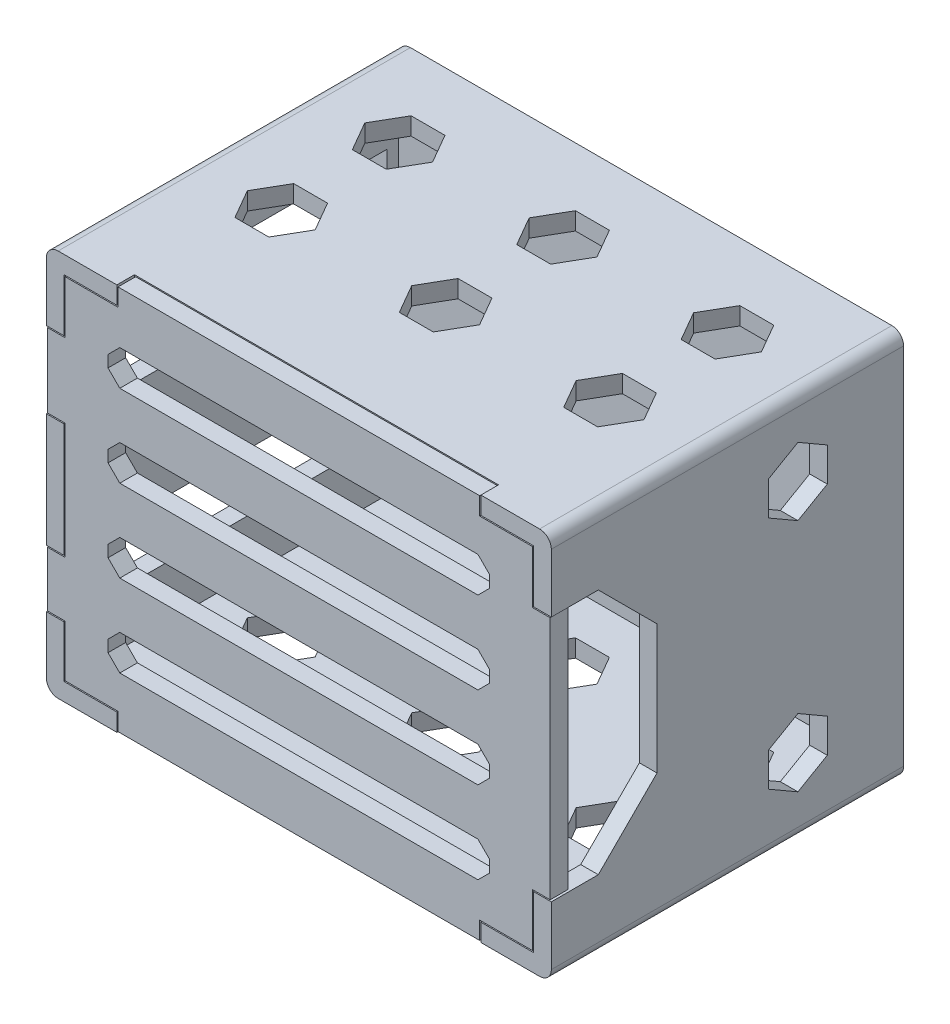
SolidWorks part; units mm, degrees
ref_plane "Front Plane" through (0, 0, 0) normal (0, 0, 1) x (1, 0, 0)
ref_plane "Top Plane" through (0, 0, 0) normal (0, 1, 0) x (1, 0, 0)
ref_plane "Right Plane" through (0, 0, 0) normal (1, 0, 0) x (0, 0, -1)
sketch "Sketch1" plane through (0, 0, 0) normal (0, 0, 1) x (1, 0, 0)
  line L0 (-43, -33) -> (-43, 33)
  line L1 (-40, -30) -> (40, -30)
  line L2 (-40, -30) -> (-40, 30)
  line L3 (-40, 30) -> (40, 30)
  line L4 (40, -30) -> (40, 30)
  line L5 (-40, -30) -> (40, 30) construction
  line L6 (-40, 30) -> (40, -30) construction
  line L7 (-43, 33) -> (43, 33)
  line L8 (43, -33) -> (43, 33)
  line L9 (-43, -33) -> (43, -33)
  point P0 (0, 0)
  dimension "D1" = 60
  dimension "125" = 80
  dimension "D3" = 3
extrude "Boss-Extrude1" add sketch "Sketch1" along normal blind 60
extrude "Boss-Extrude2" add sketch "Sketch1<2>" along normal blind 3 contours L1 L4 L3 L2 region at (0, 0, 0)
sketch "Sketch1<2>" plane through (0, 0, 0) normal (0, 0, 1) x (1, 0, 0) same geometry as "Sketch1"
sketch "Sketch2" plane through (-43, 0, 0) normal (-1, 0, 0) x (0, 0, 1)
  line L0 (60, 33) -> (60, -33) construction
  line L1 (60, -11.4) -> (5, -11.4)
  line L2 (60, -11.4) -> (60, -21.2)
  line L3 (60, -21.2) -> (5, -21.2)
  line L4 (5, -11.4) -> (5, -21.2)
  line L5 (0, 33) -> (0, -33) construction
  line L6 (60, 21) -> (5, 21)
  line L7 (60, 21) -> (60, 8)
  line L8 (60, 8) -> (5, 8)
  line L9 (5, 21) -> (5, 8)
  line L11 (60, 33) -> (0, 33) construction
  dimension "D1" = 5
  dimension "D2" = 13
  dimension "D3" = 9.8
  dimension "D4" = 19.4
  dimension "D5" = 12
extrude "Cut-Extrude1" cut sketch "Sketch2" against normal up to next
sketch "Sketch3" plane through (0, -33, 0) normal (0, -1, 0) x (1, 0, 0)
  line L0 (-43, 35) -> (43, 35) construction
  line L1 (-43, 60) -> (-43, 0) construction
  line L2 (43, 60) -> (43, 0) construction
  line L3 (-43, 15) -> (43, 15) construction
  line L9 (-25.1132, 40) -> (-30.8868, 40)
  line L14 (-30.8868, 40) -> (-33.7735, 35)
  line L15 (-33.7735, 35) -> (-30.8868, 30)
  line L20 (-30.8868, 30) -> (-25.1132, 30)
  line L21 (-25.1132, 30) -> (-22.2265, 35)
  line L22 (-43, 0) -> (43, 0) construction
  line L27 (-22.2265, 35) -> (-25.1132, 40)
  line L28 (2.8868, 40) -> (-2.8868, 40)
  line L33 (-2.8868, 40) -> (-5.7735, 35)
  line L34 (-5.7735, 35) -> (-2.8868, 30)
  line L39 (-2.8868, 30) -> (2.8868, 30)
  line L40 (2.8868, 30) -> (5.7735, 35)
  line L41 (5.7735, 35) -> (2.8868, 40)
  line L42 (30.8868, 40) -> (25.1132, 40)
  line L43 (25.1132, 40) -> (22.2265, 35)
  line L44 (22.2265, 35) -> (25.1132, 30)
  line L45 (25.1132, 30) -> (30.8868, 30)
  line L46 (30.8868, 30) -> (33.7735, 35)
  line L47 (33.7735, 35) -> (30.8868, 40)
  line L48 (30.8868, 20) -> (25.1132, 20)
  line L49 (25.1132, 20) -> (22.2265, 15)
  line L50 (22.2265, 15) -> (25.1132, 10)
  line L51 (25.1132, 10) -> (30.8868, 10)
  line L52 (30.8868, 10) -> (33.7735, 15)
  line L53 (33.7735, 15) -> (30.8868, 20)
  line L54 (2.8868, 20) -> (-2.8868, 20)
  line L55 (-2.8868, 20) -> (-5.7735, 15)
  line L56 (-5.7735, 15) -> (-2.8868, 10)
  line L57 (-2.8868, 10) -> (2.8868, 10)
  line L58 (2.8868, 10) -> (5.7735, 15)
  line L59 (5.7735, 15) -> (2.8868, 20)
  line L60 (-25.1132, 20) -> (-30.8868, 20)
  line L61 (-30.8868, 20) -> (-33.7735, 15)
  line L62 (-33.7735, 15) -> (-30.8868, 10)
  line L63 (-30.8868, 10) -> (-25.1132, 10)
  line L64 (-25.1132, 10) -> (-22.2265, 15)
  line L65 (-22.2265, 15) -> (-25.1132, 20)
  circle A0 centre (-28, 35) radius 5 construction
  circle A1 centre (0, 35) radius 5 construction
  circle A2 centre (28, 35) radius 5 construction
  circle A3 centre (28, 15) radius 5 construction
  circle A4 centre (0, 15) radius 5 construction
  circle A5 centre (-28, 15) radius 5 construction
  point P6 (-28, 35)
  point P11 (0, 35)
  point P16 (28, 35)
  point P23 (-28, 15)
  point P28 (0, 15)
  point P33 (28, 15)
  dimension "D5" = 10
  dimension "D1" = 28
  dimension "D2" = 28
  dimension "D3" = 15
  dimension "D4" = 20
extrude "Cut-Extrude2" cut sketch "Sketch3" against normal through all
sketch "Sketch4" plane through (43, 0, 0) normal (1, 0, 0) x (0, 0, -1)
  line L0 (-35, 33) -> (-35, -33) construction
  line L1 (-60, 33) -> (0, 33) construction
  line L2 (-40, -33) -> (-30, -33) construction
  line L3 (-18, 33) -> (-18, -33) construction
  line L4 (-20, -33) -> (-10, -33) construction
  line L5 (0, -33) -> (0, 33) construction
  line L7 (-40.7735, 20) -> (-37.8868, 15) construction
  line L8 (-37.8868, 15) -> (-32.1132, 15) construction
  line L9 (-32.1132, 15) -> (-29.2265, 20) construction
  line L10 (-29.2265, 20) -> (-32.1132, 25) construction
  line L11 (-32.1132, 25) -> (-37.8868, 25) construction
  line L12 (-37.8868, 25) -> (-40.7735, 20) construction
  line L13 (-18, 25.7735) -> (-23, 22.8868)
  line L14 (-23, 22.8868) -> (-23, 17.1132)
  line L15 (-23, 17.1132) -> (-18, 14.2265)
  line L16 (-18, 14.2265) -> (-13, 17.1132)
  line L17 (-13, 17.1132) -> (-13, 22.8868)
  line L18 (-13, 22.8868) -> (-18, 25.7735)
  line L19 (-18, -14.2265) -> (-23, -17.1132)
  line L20 (-23, -17.1132) -> (-23, -22.8868)
  line L21 (-23, -22.8868) -> (-18, -25.7735)
  line L22 (-18, -25.7735) -> (-13, -22.8868)
  line L23 (-13, -22.8868) -> (-13, -17.1132)
  line L24 (-13, -17.1132) -> (-18, -14.2265)
  line L25 (-40.7735, -20) -> (-37.8868, -25) construction
  line L26 (-37.8868, -25) -> (-32.1132, -25) construction
  line L27 (-32.1132, -25) -> (-29.2265, -20) construction
  line L28 (-29.2265, -20) -> (-32.1132, -15) construction
  line L29 (-32.1132, -15) -> (-37.8868, -15) construction
  line L30 (-37.8868, -15) -> (-40.7735, -20) construction
  circle A0 centre (-35, 20) radius 5 construction
  circle A1 centre (-18, 20) radius 5 construction
  circle A2 centre (-18, -20) radius 5 construction
  circle A3 centre (-35, -20) radius 5 construction
  dimension "D3" = 10
  dimension "D1" = 18
  dimension "D2" = 35
  dimension "D4" = 20
  dimension "D5" = 20
extrude "Cut-Extrude3" cut sketch "Sketch4" against normal up to next
sketch "Sketch5" plane through (0, 0, 60) normal (0, 0, 1) x (1, 0, 0)
  line L0 (43, 33) -> (-43, 33) construction
  line L1 (-31, 33) -> (31, 33)
  line L2 (-31, 33) -> (-31, 30)
  line L3 (-31, 30) -> (31, 30)
  line L4 (31, 33) -> (31, 30)
  line L5 (-40, 30) -> (40, 30) construction
  line L6 (43, -33) -> (43, 33) construction
  line L7 (-43, 33) -> (-43, 21) construction
  line L8 (-40, -30) -> (40, -30) construction
  line L9 (-31, -30) -> (31, -30)
  line L10 (-31, -30) -> (-31, -33)
  line L11 (-31, -33) -> (31, -33)
  line L12 (31, -30) -> (31, -33)
  line L13 (-43, -33) -> (43, -33) construction
  line L14 (-43, -21.2) -> (-43, -33) construction
  line L15 (40, -30) -> (40, 30) construction
  line L16 (40, 21) -> (43, 21)
  line L17 (40, 21) -> (40, -21)
  line L18 (40, -21) -> (43, -21)
  line L19 (43, 21) -> (43, -21)
  point P28 (40, 0)
  dimension "D1" = 12
  dimension "D2" = 12
  dimension "D3" = 12
  dimension "D4" = 12
  dimension "D5" = 12
extrude "Cut-Extrude4" cut sketch "Sketch5" against normal blind 3
sketch "Sketch6" plane through (0, 0, 57) normal (0, 0, 1) x (1, 0, 0)
  line L0 (-40, 21) -> (-43, 21) construction
  line L1 (-43, 21) -> (-43, 8) construction
  line L2 (-43, 8) -> (-40, 8) construction
  line L4 (-40, -11.4) -> (-43, -11.4) construction
  line L5 (-43, -11.4) -> (-43, -21.2) construction
  line L6 (-43, -21.2) -> (-40, -21.2) construction
  line L8 (-31, -30) -> (-31, -33) construction
  line L9 (-31, -33) -> (31, -33) construction
  line L10 (31, -33) -> (31, -30) construction
  line L13 (40, -21) -> (43, -21) construction
  line L14 (43, -21) -> (43, 21) construction
  line L15 (43, 21) -> (40, 21) construction
  line L16 (-31, 33) -> (-31, 30) construction
  line L18 (31, 30) -> (31, 33) construction
  line L19 (31, 33) -> (-31, 33) construction
  line L20 (-40, -30) -> (40, -30) construction
  line L21 (40, -30) -> (40, 30) construction
  line L22 (40, 30) -> (-40, 30) construction
  line L23 (-40, 30) -> (-40, -30) construction
  line L24 (-40, 21) -> (-43, 21)
  line L25 (-43, 21) -> (-43, 8)
  line L26 (-43, 8) -> (-40, 8)
  line L28 (-40, -11.4) -> (-43, -11.4)
  line L29 (-43, -11.4) -> (-43, -21.2)
  line L30 (-43, -21.2) -> (-40, -21.2)
  line L32 (-31, -30) -> (-31, -33)
  line L33 (-31, -33) -> (31, -33)
  line L34 (31, -33) -> (31, -30)
  line L37 (40, -21) -> (43, -21)
  line L38 (43, -21) -> (43, 21)
  line L39 (43, 21) -> (40, 21)
  line L40 (-31, 33) -> (-31, 30)
  line L42 (31, 30) -> (31, 33)
  line L43 (31, 33) -> (-31, 33)
  line L44 (-40, -30) -> (-31, -30)
  line L45 (40, -30) -> (40, -21)
  line L46 (40, 30) -> (31, 30)
  line L47 (-40, 30) -> (-40, 21)
  line L48 (-40, 8) -> (-40, -11.4)
  line L49 (-40, -21.2) -> (-40, -30)
  line L50 (31, -30) -> (40, -30)
  line L51 (40, 21) -> (40, 30)
  line L52 (-31, 30) -> (-40, 30)
  line L53 (39.8, 29.8) -> (30.8, 29.8)
  line L54 (30.8, 29.8) -> (30.8, 32.8)
  line L55 (30.8, 32.8) -> (-30.8, 32.8)
  line L56 (-30.8, 32.8) -> (-30.8, 29.8)
  line L57 (-30.8, 29.8) -> (-39.8, 29.8)
  line L58 (-39.8, 29.8) -> (-39.8, 20.8)
  line L59 (-39.8, 20.8) -> (-42.8, 20.8)
  line L60 (-42.8, 20.8) -> (-42.8, 8.2)
  line L61 (-42.8, 8.2) -> (-39.8, 8.2)
  line L62 (-39.8, 8.2) -> (-39.8, -11.6)
  line L63 (-39.8, -11.6) -> (-42.8, -11.6)
  line L64 (-42.8, -11.6) -> (-42.8, -21)
  line L65 (-42.8, -21) -> (-39.8, -21)
  line L66 (-39.8, -21) -> (-39.8, -29.8)
  line L67 (-39.8, -29.8) -> (-30.8, -29.8)
  line L68 (-30.8, -29.8) -> (-30.8, -32.8)
  line L69 (-30.8, -32.8) -> (30.8, -32.8)
  line L70 (30.8, -32.8) -> (30.8, -29.8)
  line L71 (30.8, -29.8) -> (39.8, -29.8)
  line L72 (39.8, -29.8) -> (39.8, -20.8)
  line L73 (39.8, -20.8) -> (42.8, -20.8)
  line L74 (42.8, -20.8) -> (42.8, 20.8)
  line L75 (42.8, 20.8) -> (39.8, 20.8)
  line L76 (39.8, 20.8) -> (39.8, 29.8)
  line M51 (40, 21) -> (40, -21)
  dimension "D1" = 0.2
extrude "Boss-Extrude3" add sketch "Sketch6" along normal blind 3 separate body contours L75 L76 L53 L54 L55 L56 L57 L58 L59 L60 L61 L62 L63 L64 L65 L66 L67 L68 L69 L70 L71 L72 L73 M51 | L74 L75 L73 M51 region at (-0.4614, 0.017, 57) region at (41.4, 0, 57)
sketch "Sketch7" plane through (0, 0, 60) normal (0, 0, 1) x (1, 0, 0)
  line L1 (-32.5, 24) -> (32.5, 24)
  line L2 (-32.5, 24) -> (-32.5, 18)
  line L3 (-32.5, 18) -> (32.5, 18)
  line L4 (32.5, 24) -> (32.5, 18)
  line L5 (-32.5, 10) -> (32.5, 10)
  line L6 (-32.5, 10) -> (-32.5, 4)
  line L7 (-32.5, 4) -> (32.5, 4)
  line L8 (32.5, 10) -> (32.5, 4)
  line L9 (-32.5, -4) -> (32.5, -4)
  line L10 (-32.5, -4) -> (-32.5, -10)
  line L11 (-32.5, -10) -> (32.5, -10)
  line L12 (32.5, -4) -> (32.5, -10)
  line L13 (-32.5, -18) -> (32.5, -18)
  line L14 (-32.5, -18) -> (-32.5, -24)
  line L15 (-32.5, -24) -> (32.5, -24)
  line L16 (32.5, -18) -> (32.5, -24)
  point P16 (0, -18)
  point P17 (0, -4)
  point P19 (0, 10)
  point P20 (0, 24)
  dimension "D1" = 6
  dimension "D2" = 65
  dimension "D3" = 4
  dimension "D4" = 4
  dimension "D5" = 8
  dimension "D6" = 8
extrude "Cut-Extrude5" cut sketch "Sketch7" against normal up to next (3 mm away)
sketch "Sketch8" plane through (0, 0, 57) normal (0, 0, 1) x (1, 0, 0)
  line L4 (40, 21) -> (40, -21)
  line L5 (40, -21) -> (43, -21)
  line L6 (43, -21) -> (43, 21)
  line L7 (43, 21) -> (40, 21)
  line L8 (40, 21) -> (40, -21)
  line L9 (40, -21) -> (43, -21)
  line L10 (43, -21) -> (43, 21)
  line L11 (43, 21) -> (40, 21)
  dimension "D1" = 0
extrude "Cut-Extrude6" cut sketch "Sketch8" against normal blind 15
chamfer "Chamfer1" distance 2 angle 45 16 edges at (-32.5, 18, 58.5) (32.5, 18, 58.5) (32.5, 24, 58.5) (-32.5, 24, 58.5) (-32.5, 10, 58.5) (32.5, 10, 58.5) (32.5, 4, 58.5) (-32.5, 4, 58.5) (32.5, -4, 58.5) (-32.5, -4, 58.5) (-32.5, -10, 58.5) (32.5, -10, 58.5) (-32.5, -24, 58.5) (-32.5, -18, 58.5) (32.5, -24, 58.5) (32.5, -18, 58.5)
fillet "Fillet1" radius 2 4 edges at (43, 33, 30) (-43, 33, 30) (43, -33, 30) (-43, -33, 30)
chamfer "Chamfer2" distance 10 angle 45 2 edges at (41.5, -21, 42) (41.5, 21, 42)
